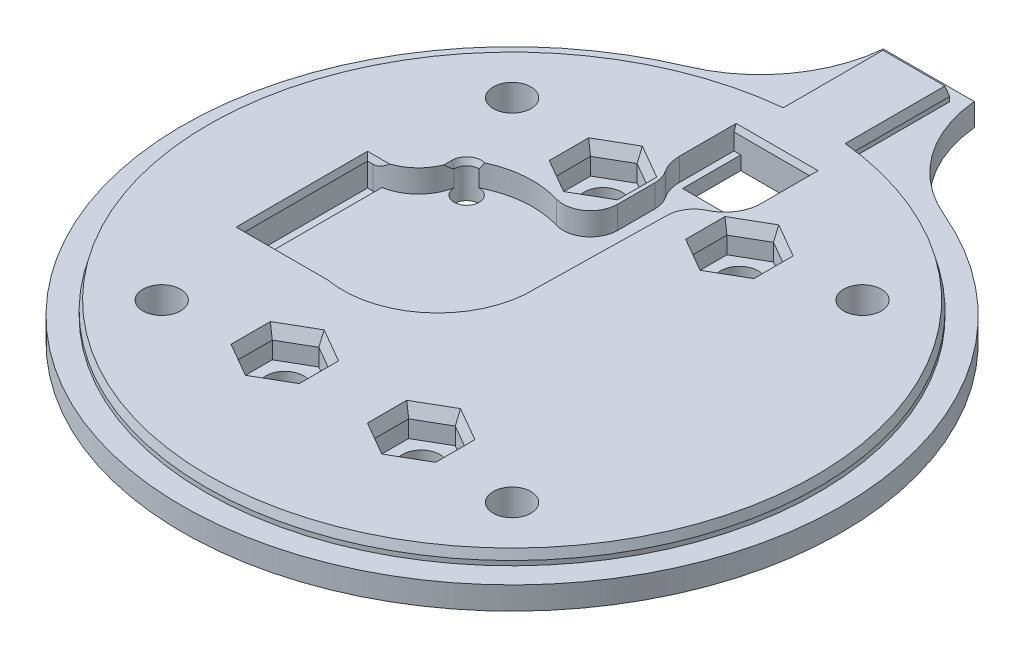
SolidWorks part; units mm, degrees
ref_plane "Спереди" through (0, 0, 0) normal (0, 0, 1) x (1, 0, 0)
ref_plane "Сверху" through (0, 0, 0) normal (0, 1, 0) x (1, 0, 0)
ref_plane "Справа" through (0, 0, 0) normal (1, 0, 0) x (0, 0, -1)
sketch "Эскиз1" plane through (0, 0, 0) normal (0, 1, 0) x (1, 0, 0)
  circle A0 centre (0, 0) radius 72.5
  dimension "D1" = 145
extrude "Бобышка-Вытянуть1" add sketch "Эскиз1" along normal blind 5
sketch "Эскиз2" plane through (0, 5, 0) normal (0, 1, 0) x (1, 0, 0)
  circle A0 centre (0, 0) radius 67.35
  dimension "D1" = 134.7
extrude "Бобышка-Вытянуть2" add sketch "Эскиз2" along normal blind 3
sketch "Эскиз3" plane through (0, 0, 0) normal (0, -1, 0) x (1, 0, 0)
  line L1 (25, -25) -> (-25, -25)
  line L2 (25, -25) -> (25, 25)
  line L3 (25, 25) -> (-25, 25)
  line L4 (-25, -25) -> (-25, 25)
  line L5 (25, -25) -> (-25, 25) construction
  line L6 (25, 25) -> (-25, -25) construction
  point P0 (0, 0)
  dimension "D1" = 50
  dimension "D2" = 50
extrude "Бобышка-Вытянуть3" add sketch "Эскиз3" along normal blind 25
sketch "Эскиз5" plane through (0, 0, 0) normal (0, -1, 0) x (1, 0, 0)
  line L1 (38.5373, -38.5373) -> (-38.5373, -38.5373) construction
  line L2 (38.5373, -38.5373) -> (38.5373, 38.5373) construction
  line L3 (38.5373, 38.5373) -> (-38.5373, 38.5373) construction
  line L4 (-38.5373, -38.5373) -> (-38.5373, 38.5373) construction
  line L5 (38.5373, -38.5373) -> (-38.5373, 38.5373) construction
  line L6 (38.5373, 38.5373) -> (-38.5373, -38.5373) construction
  circle A1 centre (38.5373, -38.5373) radius 4.15
  circle A2 centre (-38.5373, -38.5373) radius 4.15
  circle A3 centre (-38.5373, 38.5373) radius 4.15
  circle A4 centre (38.5373, 38.5373) radius 4.15
  circle A5 centre (0, 0) radius 54.5 construction
  point P0 (0, 0)
  dimension "D1" = 109
  dimension "D2" = 8.3
extrude "Вырез-Вытянуть2" cut sketch "Эскиз5" against normal through all
sketch "Эскиз6" plane through (0, 8, 0) normal (0, 1, 0) x (1, 0, 0)
  line L0 (0, 0) -> (0, 52.4) construction
  line L1 (0, 20) -> (-30, 20) construction
  circle A0 centre (0, 0) radius 67.35 construction
  circle A1 centre (-30, 20) radius 2.75
  dimension "D3" = 5.5
  dimension "D1" = 20
  dimension "D2" = 30
extrude "Вырез-Вытянуть3" cut sketch "Эскиз6" against normal through all
sketch "Sketch2" plane through (-25, 0, 0) normal (-1, 0, 0) x (0, 0, 1)
  line L0 (-25, -25) -> (25, 0) construction
  line L2 (10.125, -17.675) -> (-10.125, -17.675)
  line L3 (10.125, -17.675) -> (10.125, -7.325)
  line L4 (10.125, -7.325) -> (-10.125, -7.325)
  line L5 (-10.125, -17.675) -> (-10.125, -7.325)
  line L6 (10.125, -17.675) -> (-10.125, -7.325) construction
  line L7 (10.125, -7.325) -> (-10.125, -17.675) construction
  point P2 (0, -12.5)
  point P10 (0, -12.5)
  dimension "D1" = 20.25
  dimension "D2" = 10.35
extrude "Cut-Extrude1" cut sketch "Sketch2" against normal through all
chamfer "Chamfer1" distance 2 angle 15 1 edges at (0, 8, 67.35)
sketch "Sketch4" plane through (0, -25, 0) normal (0, -1, 0) x (1, 0, 0)
  line L0 (-25, 0) -> (25, 0) construction
  line L1 (-25, 25) -> (-25, -25) construction
  line L2 (25, -25) -> (25, 25) construction
  line L4 (25, -25) -> (-25, -25)
  line L5 (25, -25) -> (25, 25)
  line L6 (25, 25) -> (-25, 25)
  line L7 (-25, -25) -> (-25, 25)
  line L8 (25, -25) -> (-25, 25) construction
  line L9 (25, 25) -> (-25, -25) construction
  point P6 (0, 0)
extrude "Cut-Extrude3" cut sketch "Sketch4" against normal blind 12.5
sketch "Sketch5" plane through (0, -7.325, 0) normal (0, -1, 0) x (1, 0, 0)
  line L0 (0, 10.125) -> (0, -10.125) construction
  line L1 (25, 10.125) -> (-25, 10.125) construction
  line L2 (25, -10.125) -> (-25, -10.125) construction
  line L4 (25, -45) -> (-25, -45)
  line L5 (25, -45) -> (25, 45)
  line L6 (25, 45) -> (-25, 45)
  line L7 (-25, -45) -> (-25, 45)
  line L8 (25, -45) -> (-25, 45) construction
  line L9 (25, 45) -> (-25, -45) construction
  point P6 (0, 0)
  dimension "D1" = 50
  dimension "D2" = 90
extrude "Boss-Extrude2" add sketch "Sketch5" against normal up to surface (5.325 mm away) from offset 2 up to face at (-30, 0, -17.25) offset against normal yes
sketch "Sketch6" plane through (0, -5.325, 0) normal (0, -1, 0) x (1, 0, 0)
  line L0 (25, 35) -> (-25, 35) construction
  line L1 (25, 25) -> (25, 45) construction
  line L2 (-25, 45) -> (-25, 25) construction
  line L3 (25, -35) -> (-25, -35) construction
  line L4 (25, -45) -> (25, -25) construction
  line L5 (-25, -25) -> (-25, -45) construction
  line L6 (0, 45) -> (0, -45) construction
  line L7 (25, 45) -> (-25, 45) construction
  line L8 (-25, -45) -> (25, -45) construction
  line L9 (-15, 35) -> (15, -35) construction
  line L10 (-15, -35) -> (15, 35) construction
  circle A0 centre (-15, 35) radius 4.15
  circle A1 centre (-15, -35) radius 4.15
  circle A2 centre (15, 35) radius 4.15
  circle A3 centre (15, -35) radius 4.15
  point P21 (0, 0)
  point P31 (0, 0)
  dimension "D3" = 8.3
  dimension "D1" = 10
  dimension "D2" = 10
  dimension "D4" = 30
  dimension "D5" = 70
  dimension "D6" = 70
extrude "Cut-Extrude4" cut sketch "Sketch6" against normal through all
sketch "Sketch7" plane through (0, 8, 0) normal (0, 1, 0) x (1, 0, 0)
  line L1 (-15, -42.5) -> (-8.5048, -38.75)
  line L2 (-8.5048, -38.75) -> (-8.5048, -31.25)
  line L3 (-8.5048, -31.25) -> (-15, -27.5)
  line L4 (-15, -27.5) -> (-21.4952, -31.25)
  line L5 (-21.4952, -31.25) -> (-21.4952, -38.75)
  line L6 (-21.4952, -38.75) -> (-15, -42.5)
  line L7 (-15, 27.5) -> (-8.5048, 31.25)
  line L8 (-8.5048, 31.25) -> (-8.5048, 38.75)
  line L9 (-8.5048, 38.75) -> (-15, 42.5)
  line L10 (-15, 42.5) -> (-21.4952, 38.75)
  line L11 (-21.4952, 38.75) -> (-21.4952, 31.25)
  line L12 (-21.4952, 31.25) -> (-15, 27.5)
  line L13 (15, -42.5) -> (21.4952, -38.75)
  line L14 (21.4952, -38.75) -> (21.4952, -31.25)
  line L15 (21.4952, -31.25) -> (15, -27.5)
  line L16 (15, -27.5) -> (8.5048, -31.25)
  line L17 (8.5048, -31.25) -> (8.5048, -38.75)
  line L18 (8.5048, -38.75) -> (15, -42.5)
  line L19 (15, 27.5) -> (21.4952, 31.25)
  line L20 (21.4952, 31.25) -> (21.4952, 38.75)
  line L21 (21.4952, 38.75) -> (15, 42.5)
  line L22 (15, 42.5) -> (8.5048, 38.75)
  line L23 (8.5048, 38.75) -> (8.5048, 31.25)
  line L24 (8.5048, 31.25) -> (15, 27.5)
  circle A0 centre (-15, -35) radius 7.5 construction
  circle A1 centre (-15, 35) radius 7.5 construction
  circle A2 centre (15, -35) radius 7.5 construction
  circle A3 centre (15, 35) radius 7.5 construction
  dimension "D1" = 15
extrude "Cut-Extrude5" cut sketch "Sketch7" against normal blind 6.5
chamfer "Chamfer2" distance 1 angle 70 24 edges at (-11.7524, 8, 29.375) (-8.5048, 8, 35) (-11.7524, 8, 40.625) (-18.2476, 8, 40.625) (-21.4952, 8, 35) (-18.2476, 8, 29.375) (-11.7524, 8, -29.375) (-8.5048, 8, -35) (-11.7524, 8, -40.625) (-18.2476, 8, -40.625) (-21.4952, 8, -35) (-18.2476, 8, -29.375) (11.7524, 8, -40.625) (18.2476, 8, -40.625) (21.4952, 8, -35) (18.2476, 8, -29.375) (11.7524, 8, -29.375) (8.5048, 8, -35) (11.7524, 8, 29.375) (18.2476, 8, 29.375) (21.4952, 8, 35) (18.2476, 8, 40.625) (11.7524, 8, 40.625) (8.5048, 8, 35)
sketch "Sketch8" plane through (0, 8, 0) normal (0, 1, 0) x (1, 0, 0)
  line L1 (-26.25, 11.95) -> (-43.75, 11.95)
  line L2 (-26.25, 11.95) -> (-26.25, -15.95)
  line L3 (-26.25, -15.95) -> (-43.75, -15.95)
  line L4 (-43.75, 11.95) -> (-43.75, -15.95)
  line L5 (-26.25, 11.95) -> (-43.75, -15.95) construction
  line L6 (-26.25, -15.95) -> (-43.75, 11.95) construction
  point P0 (-35, -2)
  dimension "D1" = 27.9
  dimension "D2" = 17.5
  dimension "D3" = 35
  dimension "D4" = 2
extrude "Cut-Extrude6" cut sketch "Sketch8" against normal blind 5
chamfer "Chamfer3" distance 10 angle 45 4 edges at (25, -2.6625, 45) (25, -2.6625, -45) (-25, -2.6625, -45) (-25, -2.6625, 45)
chamfer "Chamfer6" distance 3 angle 30 4 edges at (-25, -2.6625, -35) (-25, -2.6625, 35) (25, -2.6625, 35) (25, -2.6625, -35)
sketch "Sketch10" plane through (0, 8, 0) normal (0, 1, 0) x (1, 0, 0)
  line L0 (-32.75, 20) -> (-32.75, 11.95)
  line L1 (-26.25, 11.95) -> (-43.75, 11.95) construction
  line L2 (-32.75, 11.95) -> (-26.25, 11.95)
  line L3 (-26.25, 11.95) -> (-26.25, -15.95)
  circle A0 centre (-30, 20) radius 2.75 construction
  arc A1 (-26.25, -15.95) -> (-30, 22.75) centre (-20.4864, 4.1402) ccw
  arc A2 (-30, 22.75) -> (-32.75, 20) centre (-30, 20) ccw
extrude "Cut-Extrude8" cut sketch "Sketch10" against normal up to surface (5 mm away) up to face at (-35, 3, 2)
chamfer "Chamfer7" distance 0.5 angle 70 6 edges at (-31.9445, 8, -21.9445) (-32.75, 8, -15.975) (0.3167, 8, -6.156) (-38.25, 8, -11.95) (-43.75, 8, 2) (-35, 8, 15.95)
sketch "Sketch11" plane through (0, 3, 0) normal (0, 1, 0) x (1, 0, 0)
  line L0 (-42.25, -15.95) -> (-42.25, 11.95) construction
  line L1 (-43.75, -15.95) -> (-26.25, -15.95) construction
  line L2 (-32.75, 11.95) -> (-43.75, 11.95) construction
  line L4 (-40.75, 11.95) -> (-43.75, 11.95)
  line L5 (-40.75, 11.95) -> (-40.75, -15.95)
  line L6 (-40.75, -15.95) -> (-43.75, -15.95)
  line L7 (-43.75, 11.95) -> (-43.75, -15.95)
  line L8 (-40.75, 11.95) -> (-43.75, -15.95) construction
  line L9 (-40.75, -15.95) -> (-43.75, 11.95) construction
  point P6 (-42.25, -2)
  dimension "D1" = 3
extrude "Cut-Extrude9" cut sketch "Sketch11" against normal blind 1.5
chamfer "Chamfer8" distance 1 angle 45 2 edges at (0, -12.5, 10.125) (0, -12.5, -10.125)
sketch "Sketch12" plane through (0, 0, 0) normal (0, -1, 0) x (1, 0, 0)
  line L0 (0, 0) -> (-65, 0) construction
  line L1 (-65, -17.5) -> (-65, 17.5)
  line L2 (-65, -17.5) -> (-70.3562, -17.5)
  line L3 (-65, 17.5) -> (-70.3562, 17.5)
  line L4 (-70.3562, 17.5) -> (-70.3562, -17.5)
  circle A0 centre (0, 0) radius 72.5 construction
  circle A1 centre (0, 0) radius 72.5 construction
  point P6 (-65, 0)
  dimension "D1" = 65
  dimension "D2" = 35
extrude "Boss-Extrude3" add sketch "Sketch12" against normal up to surface (5 mm away) up to face at (0, 5, 67.35)
sketch "Sketch13" plane through (0, 0, 0) normal (0, -1, 0) x (1, 0, 0)
  line L0 (0, 0) -> (0, -84.9584) construction
  line L2 (10, -51.66) -> (-10, -51.66)
  line L3 (10, -51.66) -> (10, -91.66)
  line L4 (10, -91.66) -> (-10, -91.66)
  line L5 (-10, -51.66) -> (-10, -91.66)
  line L6 (10, -51.66) -> (-10, -91.66) construction
  line L7 (10, -91.66) -> (-10, -51.66) construction
  point P4 (0, -71.66)
  dimension "D1" = 71.66
  dimension "D2" = 20
  dimension "D3" = 40
extrude "Boss-Extrude5" add sketch "Sketch13" against normal up to surface (5 mm away) up to face at (0, 5, 72.5)
fillet "Fillet2" radius 30 2 edges at (-10, 2.5, -71.807) (10, 2.5, -71.807)
sketch "Sketch14" plane through (0, 8, 0) normal (0, 1, 0) x (1, 0, 0)
  line L0 (0, 0) -> (0, 97.0859) construction
  line L2 (-7.35, 88.9086) -> (7.35, 88.9086)
  line L3 (-7.35, 88.9086) -> (-7.35, 66.4086)
  line L4 (-7.35, 66.4086) -> (7.35, 66.4086)
  line L5 (7.35, 88.9086) -> (7.35, 66.4086)
  line L6 (-7.35, 88.9086) -> (7.35, 66.4086) construction
  line L7 (-7.35, 66.4086) -> (7.35, 88.9086) construction
  circle A0 centre (0, 0) radius 66.8141 construction
  point P3 (0, 77.6586)
  dimension "D1" = 14.7
  dimension "D2" = 22.5
extrude "Boss-Extrude6" add sketch "Sketch14" against normal up to surface (3 mm away)
chamfer "Chamfer9" distance 2 angle 15 3 edges at (-7.35, 8, -77.6586) (0, 8, -88.9086) (7.35, 8, -77.6586)
sketch "Sketch16" plane through (0, 3, 0) normal (0, 1, 0) x (1, 0, 0)
  line L0 (0, 0) -> (0, 51.4) construction
  line L3 (-15, 45) -> (15, 45) construction
  line L4 (7.5, 45) -> (-7.5, 45)
  line L5 (7.5, 45) -> (7.5, 57.8)
  line L6 (7.5, 57.8) -> (-7.5, 57.8)
  line L7 (-7.5, 45) -> (-7.5, 57.8)
  line L8 (7.5, 45) -> (-7.5, 57.8) construction
  line L9 (7.5, 57.8) -> (-7.5, 45) construction
  point P7 (0, 51.4)
  dimension "D1" = 15
  dimension "D2" = 12.8
extrude "Cut-Extrude11" cut sketch "Sketch16" against normal through all and the other way through all
sketch "Sketch19" plane through (0, 8, 0) normal (0, 1, 0) x (1, 0, 0)
  line L0 (7.5, 57.8) -> (-7.5, 57.8) construction
  line L1 (-1, 37.8) -> (1, 37.8)
  line L2 (-9, 45.8) -> (-9, 57.8)
  line L3 (-9, 57.8) -> (9, 57.8)
  line L4 (9, 45.8) -> (9, 57.8)
  line L5 (-9, 37.8) -> (9, 57.8) construction
  line L6 (-9, 57.8) -> (9, 37.8) construction
  line L7 (0, 0) -> (0, 57.8) construction
  arc A0 (-9, 45.8) -> (-1, 37.8) centre (-1, 45.8) ccw
  arc A1 (1, 37.8) -> (9, 45.8) centre (1, 45.8) ccw
  point P0 (0, 47.8)
  dimension "D3" = 8
  dimension "D1" = 18
  dimension "D2" = 20
extrude "Cut-Extrude12" cut sketch "Sketch19" against normal up to surface (5 mm away) up to face at (-28.5815, 3, -5.6977)
sketch "Sketch20" plane through (0, 8, 0) normal (0, 1, 0) x (1, 0, 0)
  line L0 (1, 37.8) -> (0.3445, 2.4352)
  line L1 (-6.6569, 40.1431) -> (-6.6569, 19.8111)
  line L2 (1, 37.8) -> (-1, 37.8)
  line L3 (0.3445, 2.4352) -> (-6.6569, 19.8111)
  arc A1 (-9, 45.8) -> (-1, 37.8) centre (-1, 45.8) ccw construction
  arc A3 (-1, 37.8) -> (-6.6569, 40.1431) centre (-1, 45.8) cw
  arc A6 (-26.25, -15.95) -> (-30, 22.75) centre (-20.4864, 4.1402) ccw construction
  arc A8 (-24.0751, -16.45) -> (-29.1828, 23.1456) centre (-20.4864, 4.1402) ccw construction
  dimension "D1" = 35.3648
extrude "Cut-Extrude13" cut sketch "Sketch20" against normal up to surface (5 mm away) up to face at (-28.5815, 3, -5.6977)
fillet "Fillet4" radius 6 3 edges at (-6.6569, 5.5, -19.8111) (-6.6569, 5.5, -40.1431) (1, 5.5, -37.8)
chamfer "Chamfer10" distance 0.5 angle 70 1 edges at (0, 8, -57.8)
sketch "Sketch21" plane through (0, 0, 0) normal (0, -1, 0) x (1, 0, 0)
  line L0 (-15.6633, -76.7088) -> (15.6633, -76.7088) construction
  arc A0 (-10, -91.66) -> (-28.2022, -66.7899) centre (-39.8721, -94.427) ccw construction
  arc A1 (28.2022, -66.7899) -> (10, -91.66) centre (39.8721, -94.427) ccw construction
  text T0 "<b>FTCR</b>" font "Arial" height 8
extrude "Boss-Extrude8" add sketch "Sketch21" along normal blind 1
fillet "Fillet5" radius 10 1 edges at (-32.75, 4.8131, -11.95)
